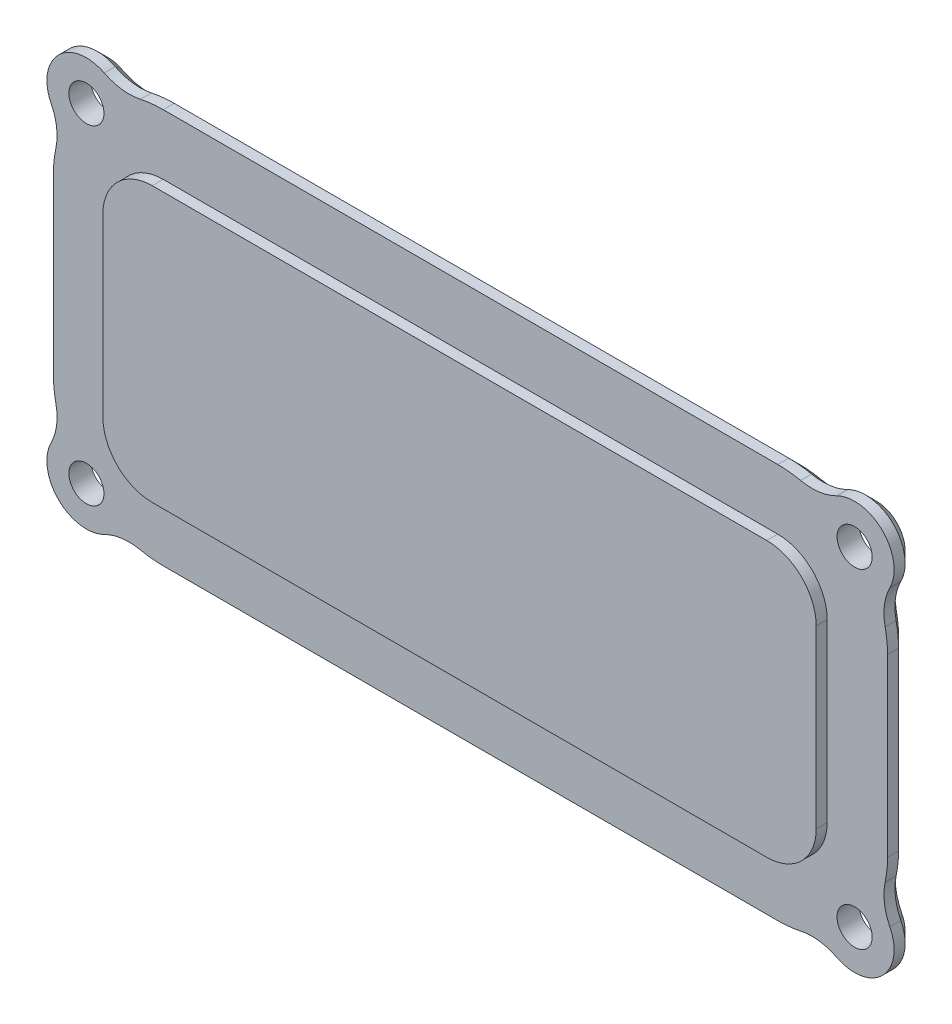
SolidWorks part; units mm, degrees
ref_plane "Front Plane" through (0, 0, 0) normal (0, 0, 1) x (1, 0, 0)
ref_plane "Top Plane" through (0, 0, 0) normal (0, 1, 0) x (1, 0, 0)
ref_plane "Right Plane" through (0, 0, 0) normal (1, 0, 0) x (0, 0, -1)
ref_axis "X" through (-88.99, 0, 0) along (1, 0, 0)
ref_axis "Y" through (0, 55, 0) along (0, -1, 0)
ref_axis "Z" through (0, 0, -88.99) along (0, 0, 1)
sketch "Sketch1" plane through (0, 0, 0) normal (0, 0, 1) x (1, 0, 0)
  line L5 (38, -8) -> (38, 8)
  line L6 (28, 18) -> (-28, 18)
  line L7 (-38, 8) -> (-38, -8)
  line L8 (-28, -18) -> (28, -18)
  line L9 (33, -8) -> (33, 8)
  line L10 (28, 13) -> (-28, 13)
  line L11 (-33, 8) -> (-33, -8)
  line L12 (-28, -13) -> (28, -13)
  line L13 (33, -8) -> (33, 8) construction
  line L14 (28, 13) -> (-28, 13) construction
  line L15 (-33, 8) -> (-33, -8) construction
  line L16 (-28, -13) -> (28, -13) construction
  line L17 (32.5, -8) -> (32.5, 8)
  line L18 (28, 12.5) -> (-28, 12.5)
  line L19 (-32.5, 8) -> (-32.5, -8)
  line L20 (-28, -12.5) -> (28, -12.5)
  line L21 (0, 0) -> (0, 13) construction
  line L22 (-35, -15) -> (35, 15) construction
  line L23 (0, 0) -> (33, 0) construction
  arc A0 (38, 8) -> (37.7819, 10.0772) centre (28, 8) ccw
  arc A1 (-28, 18) -> (-30.0772, 17.7819) centre (-28, 8) ccw
  arc A2 (-38, -8) -> (-37.7819, -10.0772) centre (-28, -8) ccw
  arc A3 (28, -18) -> (30.0772, -17.7819) centre (28, -8) ccw
  arc A4 (28, -13) -> (33, -8) centre (28, -8) ccw
  arc A5 (33, 8) -> (28, 13) centre (28, 8) ccw
  arc A6 (-28, 13) -> (-33, 8) centre (-28, 8) ccw
  arc A7 (-33, -8) -> (-28, -13) centre (-28, -8) ccw
  arc A8 (28, -13) -> (33, -8) centre (28, -8) ccw construction
  arc A9 (33, 8) -> (28, 13) centre (28, 8) ccw construction
  arc A10 (-28, 13) -> (-33, 8) centre (-28, 8) ccw construction
  arc A12 (32.5, 8) -> (28, 12.5) centre (28, 8) ccw
  arc A13 (-28, 12.5) -> (-32.5, 8) centre (-28, 8) ccw
  arc A14 (-32.5, -8) -> (-28, -12.5) centre (-28, -8) ccw
  arc A15 (28, -12.5) -> (32.5, -8) centre (28, -8) ccw
  circle A19 centre (35, 15) radius 1.6 construction
  circle A23 centre (35, 15) radius 1.6
  arc A25 (38.2119, 13.374) -> (33.374, 18.2119) centre (35, 15) ccw
  arc A28 (33.374, 18.2119) -> (30.0772, 17.7819) centre (31.1157, 22.6728) cw
  arc A29 (38.2119, 13.374) -> (37.7819, 10.0772) centre (42.6728, 11.1157) ccw
  arc A30 (-38.2119, 13.374) -> (-37.7819, 10.0772) centre (-42.6728, 11.1157) cw
  arc A31 (-33.374, 18.2119) -> (-30.0772, 17.7819) centre (-31.1157, 22.6728) ccw
  circle A32 centre (-35, 15) radius 1.6
  arc A33 (-38.2119, 13.374) -> (-33.374, 18.2119) centre (-35, 15) cw
  arc A34 (38.2119, -13.374) -> (37.7819, -10.0772) centre (42.6728, -11.1157) cw
  arc A35 (33.374, -18.2119) -> (30.0772, -17.7819) centre (31.1157, -22.6728) ccw
  circle A36 centre (35, -15) radius 1.6
  arc A37 (38.2119, -13.374) -> (33.374, -18.2119) centre (35, -15) cw
  arc A38 (-33.374, -18.2119) -> (-30.0772, -17.7819) centre (-31.1157, -22.6728) cw
  circle A39 centre (-35, -15) radius 1.6
  arc A40 (-38.2119, -13.374) -> (-37.7819, -10.0772) centre (-42.6728, -11.1157) ccw
  arc A41 (-38.2119, -13.374) -> (-33.374, -18.2119) centre (-35, -15) ccw
  arc A42 (30.0772, 17.7819) -> (28, 18) centre (28, 8) ccw
  arc A43 (-37.7819, 10.0772) -> (-38, 8) centre (-28, 8) ccw
  arc A44 (38, 8) -> (28, 18) centre (28, 8) ccw construction
  arc A45 (37.7819, -10.0772) -> (38, -8) centre (28, -8) ccw
  arc A46 (-30.0772, -17.7819) -> (-28, -18) centre (-28, -8) ccw
  arc A47 (28, -18) -> (38, -8) centre (28, -8) ccw construction
  arc A48 (-28, 18) -> (-38, 8) centre (-28, 8) ccw construction
  arc A50 (-38, -8) -> (-28, -18) centre (-28, -8) ccw construction
  circle A51 centre (35, 15) radius 3.6 construction
  arc A52 (-33, -8) -> (-28, -13) centre (-28, -8) ccw construction
  point P83 (38.6, 15)
  dimension "D5" = 5
  dimension "D1" = 0
  dimension "D2" = 5
  dimension "D3" = 0.5
  dimension "D4" = 2
extrude "Boss-Extrude1" add sketch "Sketch1" against normal blind 2 contours L6 A1 A31 A33 A30 A43 L7 A2 A40 A41 A38 A46 L8 A3 A35 A37 A34 A45 L5 A0 A29 A25 A28 A42 | A23 | A36 | A39 | A32
extrude "Boss-Extrude2" add sketch "Sketch1<3>" along normal blind 1 contours L20 A15 L17 A12 L18 A13 L19 A14 region at (0, 0, 0)
sketch "Sketch1<3>" plane through (0, 0, 0) normal (0, 0, 1) x (1, 0, 0) same geometry as "Sketch1"
chamfer "Chamfer1" distance 1 angle 45 24 edges at (-38, 0, -2) (-37.9453, -9.0443, -2) (-37.9453, 9.0443, -2) (-37.7148, -11.7624, -2) (-37.7148, 11.7624, -2) (-37.5456, -17.5456, -2) (-37.5456, 17.5456, -2) (-31.7624, -17.7148, -2) (-31.7624, 17.7148, -2) (-29.0443, -17.9453, -2) (-29.0443, 17.9453, -2) (0, -18, -2) (0, 18, -2) (29.0443, -17.9453, -2) (29.0443, 17.9453, -2) (31.7624, -17.7148, -2) (31.7624, 17.7148, -2) (37.5456, -17.5456, -2) (37.5456, 17.5456, -2) (37.7148, -11.7624, -2) (37.7148, 11.7624, -2) (37.9453, -9.0443, -2) (37.9453, 9.0443, -2) (38, 0, -2)
